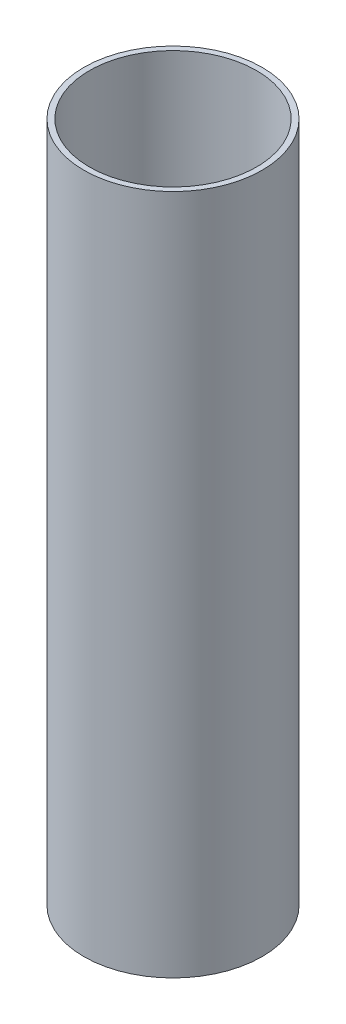
SolidWorks part; units mm, degrees
material "Fuzed Silica"
ref_plane "Front Plane" through (0, 0, 0) normal (0, 0, 1) x (1, 0, 0)
ref_plane "Top Plane" through (0, 0, 0) normal (0, 1, 0) x (1, 0, 0)
ref_plane "Right Plane" through (0, 0, 0) normal (1, 0, 0) x (0, 0, -1)
sketch "Sketch1" plane through (0, 0, 0) normal (0, 1, 0) x (1, 0, 0)
  circle A0 centre (0, 0) radius 37.5
  circle A1 centre (0, 0) radius 40
  dimension "D1" = 80
  dimension "D2" = 75
extrude "Boss-Extrude1" add sketch "Sketch1" along normal blind 305.6
